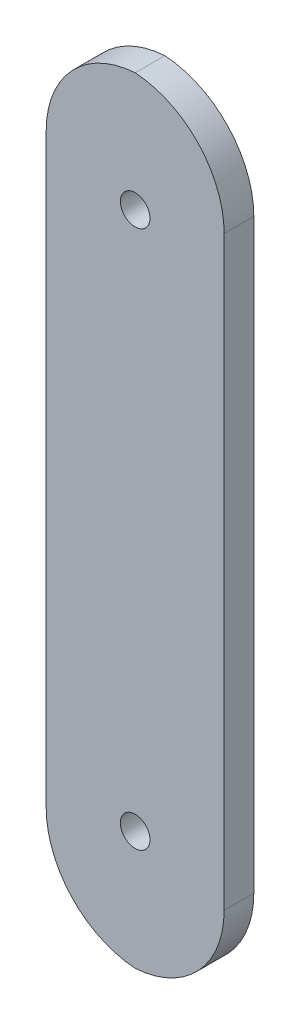
SolidWorks part; units mm, degrees
ref_plane "Front Plane" through (0, 0, 0) normal (0, 0, 1) x (1, 0, 0)
ref_plane "Top Plane" through (0, 0, 0) normal (0, 1, 0) x (1, 0, 0)
ref_plane "Right Plane" through (0, 0, 0) normal (1, 0, 0) x (0, 0, -1)
sketch "Sketch2" plane through (0, 0, 0) normal (0, 0, 1) x (1, 0, 0)
  line L1 (0, 0) -> (-19.05, 0)
  line L2 (0, 0) -> (0, 83.058)
  line L3 (0, 83.058) -> (-19.05, 83.058)
  line L4 (-19.05, 0) -> (-19.05, 83.058)
  dimension "D1" = 83.058
  dimension "D2" = 19.05
extrude "Boss-Extrude1" add sketch "Sketch2" along normal blind 3.175
fillet "Fillet1" radius 10.16 4 edges at (-19.05, 0, 1.5875) (0, 0, 1.5875) (-19.05, 83.058, 1.5875) (0, 83.058, 1.5875)
sketch "Sketch3" plane through (0, 0, 3.175) normal (0, 0, 1) x (1, 0, 0)
  line L0 (-19.05, 72.898) -> (-19.05, 10.16) construction
  line L1 (0, 10.16) -> (0, 72.898) construction
  circle A0 centre (-9.525, 12.7199) radius 1.5875
  circle A2 centre (-9.525, 70.3381) radius 1.5875
  dimension "D1" = 12.7
  dimension "D2" = 9.525
  dimension "D3" = 3.175
  dimension "D4" = 3.175
  dimension "D5" = 9.525
  dimension "D6" = 12.7
extrude "Cut-Extrude1" cut sketch "Sketch3" against normal blind 3.175
